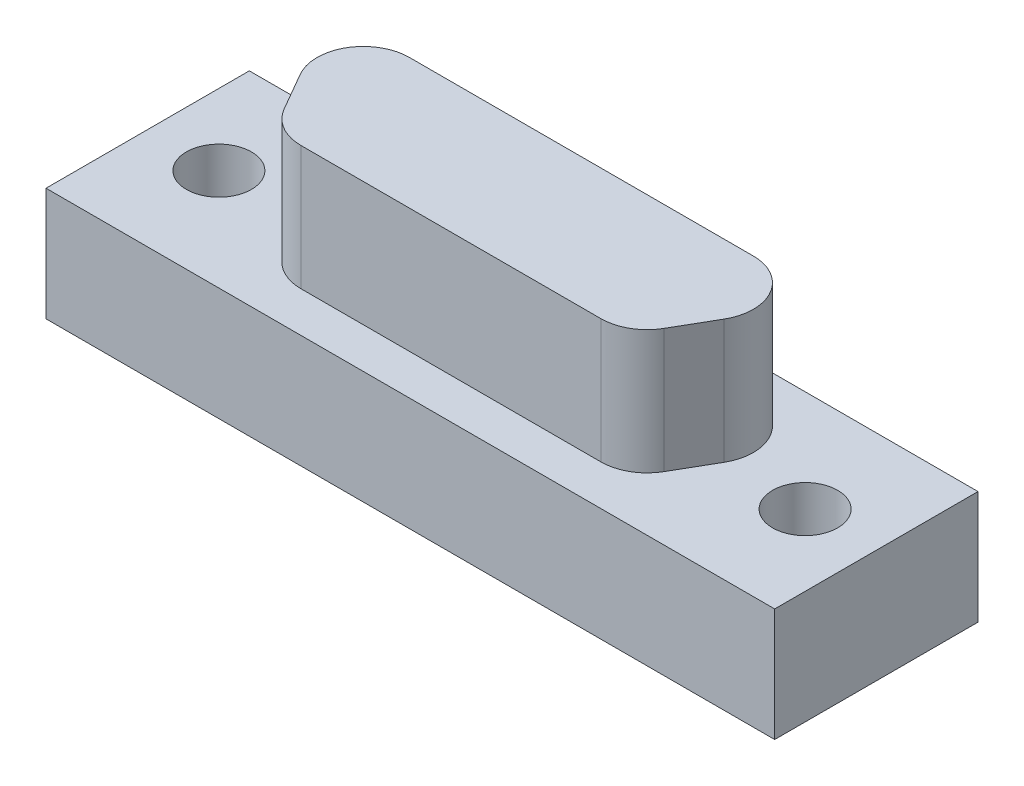
SolidWorks part; units mm, degrees
ref_plane "Front Plane" through (0, 0, 0) normal (0, 0, 1) x (1, 0, 0)
ref_plane "Top Plane" through (0, 0, 0) normal (0, 1, 0) x (1, 0, 0)
ref_plane "Right Plane" through (0, 0, 0) normal (1, 0, 0) x (0, 0, -1)
sketch "Sketch1" plane through (0, 0, 0) normal (0, 1, 0) x (1, 0, 0)
  line L0 (19.2803, -6.105) -> (8.0415, -6.105)
  line L1 (0, 0) -> (27.31, 0)
  line L2 (0, 0) -> (0, -7.62)
  line L3 (0, -7.62) -> (27.31, -7.62)
  line L4 (27.31, 0) -> (27.31, -7.62)
  line L5 (5.605, -2.06) -> (21.705, -2.06)
  line L6 (5.605, -2.06) -> (5.605, -5.56)
  line L7 (5.605, -5.56) -> (21.705, -5.56)
  line L8 (21.705, -2.06) -> (21.705, -5.56)
  line L9 (6.5433, -5.24) -> (5.7176, -3.81)
  line L10 (7.2159, -1.215) -> (20.1059, -1.215)
  line L11 (21.6041, -3.81) -> (20.7785, -5.24)
  circle A0 centre (2.67, -3.81) radius 1.22
  circle A1 centre (24.64, -3.81) radius 1.22
  arc A2 (8.0415, -6.105) -> (6.5433, -5.24) centre (8.0415, -4.375) cw
  arc A3 (5.7176, -3.81) -> (5.4859, -2.945) centre (7.2159, -2.945) cw
  arc A4 (5.4859, -2.945) -> (7.2159, -1.215) centre (7.2159, -2.945) cw
  arc A5 (20.1059, -1.215) -> (21.6041, -3.81) centre (20.1059, -2.945) cw
  arc A6 (20.7785, -5.24) -> (19.2803, -6.105) centre (19.2803, -4.375) cw
  point P27 (0, 0)
  dimension "D6" = 2.44
  dimension "D1" = 27.31
  dimension "D2" = 7.62
  dimension "D3" = 3.81
  dimension "D4" = 21.97
  dimension "D5" = 2.67
  dimension "D7" = 16.1
  dimension "D8" = 5.605
  dimension "D9" = 3.5
  dimension "D10" = 2.06
extrude "Boss-Extrude1" add sketch "Sketch1" along normal blind 4.24 contours L4 L1 L2 L3 A1 A0 L7 A6 L0 A2 L6 A3 A4 L5 L10 A5 L8 | L9 A3 L6 L7 A2 | A6 L7 A2 L0 | A5 L10 A4 L5 | L11 A6 L7 L8 A5 | A5 L8 | A4 A3 L6 | L6 A4 L5 | L5 A5 L8 region at (13.6609, 0, 5.8256) region at (21.3313, 0, 4.9201) region at (5.9825, 0, 4.9129) region at (21.7575, 0, 2.945) region at (5.5572, 0, 2.945) region at (21.6686, 0, 2.1326) region at (5.6451, 0, 2.1416) region at (13.6609, 0, 1.6482) region at (13.655, 0, 0.2835)
extrude "Boss-Extrude2" add sketch "Sketch1<2>" along normal blind 8.89 contours A5 L10 A4 L5 | A6 L7 A2 L0 | A6 L11 A5 L8 L5 A4 L6 A3 L9 A2 L7 | A4 A3 L6 | A5 L8 region at (13.6609, 0, 5.8256) region at (13.6586, 0, 3.7664) region at (21.7575, 0, 2.945) region at (5.5572, 0, 2.945) region at (13.6609, 0, 1.6482)
sketch "Sketch1<2>" plane through (0, 0, 0) normal (0, 1, 0) x (1, 0, 0) same geometry as "Sketch1"
sketch "Sketch2" plane through (0, 8.89, 0) normal (0, 1, 0) x (1, 0, 0)
  line L0 (19.3584, -6.339) -> (8.1196, -6.339)
  line L1 (6.6214, -5.474) -> (5.7958, -4.044)
  line L2 (7.294, -1.449) -> (20.184, -1.449)
  line L3 (21.6822, -4.044) -> (20.8566, -5.474)
  arc A0 (8.1196, -6.339) -> (6.6214, -5.474) centre (8.1196, -4.609) cw
  arc A1 (5.7958, -4.044) -> (5.564, -3.179) centre (7.294, -3.179) cw
  arc A2 (5.564, -3.179) -> (7.294, -1.449) centre (7.294, -3.179) cw
  arc A3 (20.184, -1.449) -> (21.6822, -4.044) centre (20.184, -3.179) cw
  arc A4 (20.8566, -5.474) -> (19.3584, -6.339) centre (19.3584, -4.609) cw
equation "\"D5@Sketch1\"=(\"D1@Sketch1\"-\"D4@Sketch1\")/2"
equation "\"D8@Sketch1\"=(\"D1@Sketch1\"-\"D7@Sketch1\")/2"
equation "\"D10@Sketch1\"= (\"D2@Sketch1\"-\"D9@Sketch1\")/2"
